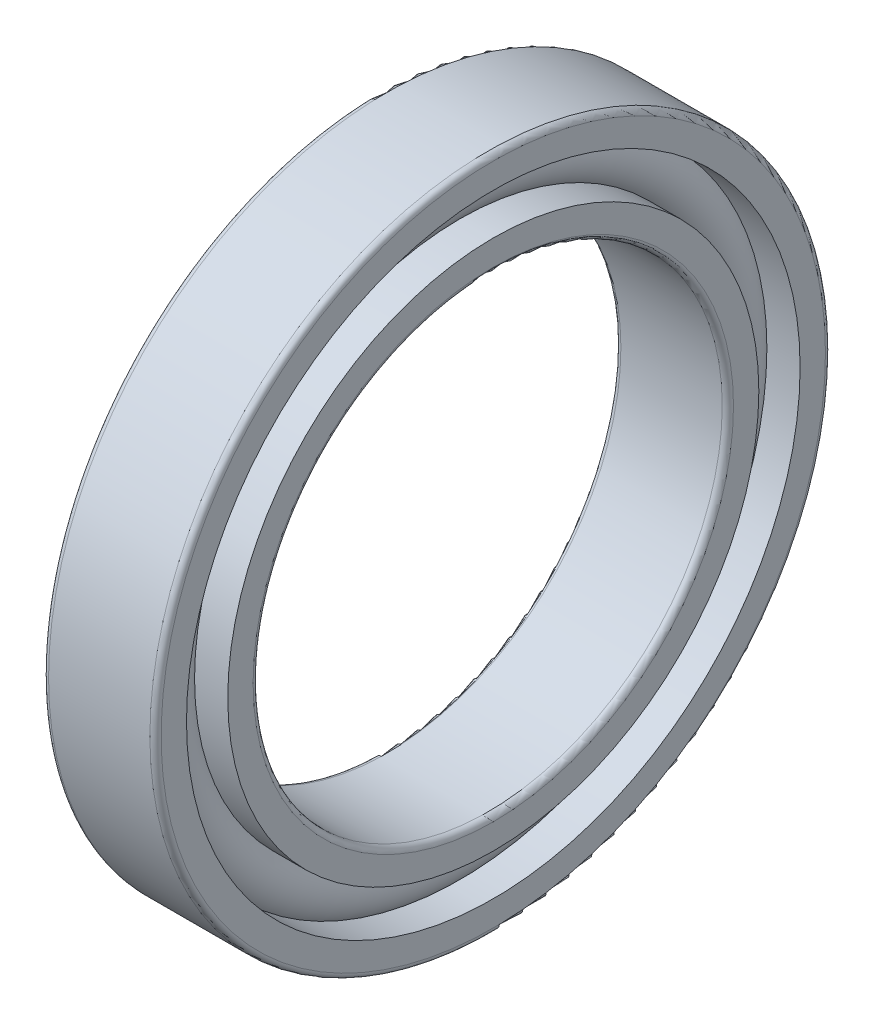
SolidWorks part; units mm, degrees
ref_plane "Plane1" through (0, 0, 0) normal (0, 0, 1) x (1, 0, 0)
ref_plane "Plane2" through (0, 0, 0) normal (0, 1, 0) x (1, 0, 0)
ref_plane "Plane3" through (0, 0, 0) normal (1, 0, 0) x (0, 0, -1)
sketch "Clipboard" plane through (0, 0, 0) normal (0, 0, 1) x (1, 0, 0)
  line L0 (-10, 0) -> (10, 0) construction
  line L1 (0, 0) -> (22.3471, -0.7804)
  line L2 (0, 0) -> (30.4814, 1.0644)
  line L3 (0, 0) -> (22.3471, -0.7804)
  line L4 (0, 0) -> (-22.3573, -0.3902)
  dimension "BallCLRad" = 30.5
sketch "CagSpiSke" plane through (0, 0, 0) normal (0, 0, 1) x (1, 0, 0)
  line L0 (0.33, 29.95) -> (0.33, 31.05)
  line L1 (0.33, 31.05) -> (-0.33, 31.05)
  line L2 (-0.33, 31.05) -> (-0.33, 29.95)
  line L3 (-0.33, 29.95) -> (0.33, 29.95)
  line L4 (-20.6375, 0) -> (20.6375, 0) construction
  line L5 (0, 0) -> (0, 23.7692) construction
  dimension "OD" = 62.1
  dimension "ID" = 59.9
revolve "CageSpine" add sketch "CagSpiSke" angle 0.001 about L4 reverse direction yes
ref_axis "Axis1" through (-50, 0, 0) along (1, 0, 0)
sketch "CagBalSke" plane through (0, 0, 0) normal (0, 0, 1) x (1, 0, 0)
  line L0 (-3.63, 30.5) -> (3.63, 30.5)
  line L1 (-1.905, 30.5) -> (1.905, 30.5) construction
  line L2 (-10, 0) -> (10, 0) construction
  line L3 (0, 0) -> (0, 24) construction
  arc A0 (3.63, 30.5) -> (-3.63, 30.5) centre (0, 30.5) cw
  dimension "BallCLRad" = 30.5
revolve "CageBall" [suppressed] add sketch "CagBalSke" angle 360 about L1 reverse direction yes
pattern_circular "CageBalls" [suppressed] count 2 every 180 about axis through (-50, 0, 0) along (1, 0, 0)
sketch "CagTrmODSke" plane through (0, 0, 0) normal (0, 0, 1) x (1, 0, 0)
  line L0 (3.631, 31.05) -> (3.631, 34.131)
  line L1 (3.631, 34.131) -> (-3.631, 34.131)
  line L2 (-3.631, 34.131) -> (-3.631, 31.05)
  line L3 (-3.631, 31.05) -> (3.631, 31.05)
  line L4 (-20.6375, 0) -> (20.6375, 0) construction
  line L5 (0, 0) -> (0, 25) construction
  dimension "Width" = 7.262
  dimension "ID" = 62.1
  dimension "OD" = 68.262
revolve "CageTrimOD" [suppressed] cut sketch "CagTrmODSke" angle 360 about L4 reverse direction yes
sketch "CagTrmIDSke" plane through (0, 0, 0) normal (0, 0, 1) x (1, 0, 0)
  line L0 (3.631, 26.871) -> (3.631, 29.95)
  line L1 (3.631, 29.95) -> (-3.631, 29.95)
  line L2 (-3.631, 29.95) -> (-3.631, 26.871)
  line L3 (-3.631, 26.871) -> (3.631, 26.871)
  line L4 (-20.6375, 0) -> (20.6375, 0) construction
  line L5 (0, 0) -> (0, 25) construction
  dimension "Width" = 7.262
  dimension "ID" = 53.742
  dimension "OD" = 59.9
revolve "CageTrimID" [suppressed] cut sketch "CagTrmIDSke" angle 360 about L4 reverse direction yes
sketch "BalSimSke" plane through (0, 0, 0) normal (0, 0, 1) x (1, 0, 0)
  line L0 (-10, 0) -> (10, 0) construction
  line L1 (-10, 30.5) -> (10, 30.5) construction
  line L2 (0, 0) -> (0, 23) construction
  circle A0 centre (0, 30.5) radius 3.3
  dimension "BallCLRad" = 30.5
  dimension "Ball_diameter" = 6.6
revolve "BallsSimplified" add sketch "BalSimSke" angle 360 about L0
sketch "BalDetSke" plane through (0, 0, 0) normal (0, 0, 1) x (1, 0, 0)
  line L0 (-3.3, 30.5) -> (3.3, 30.5)
  line L1 (-1.905, 30.5) -> (1.905, 30.5) construction
  line L2 (0, 0) -> (0, 25) construction
  arc A0 (3.3, 30.5) -> (-3.3, 30.5) centre (0, 30.5) cw
  dimension "BallCLRad" = 30.5
  dimension "Ball_diameter" = 6.6
revolve "BallDetailed" [suppressed] add sketch "BalDetSke" angle 360 about L1 reverse direction yes
sketch "InnRacSke" plane through (0, 0, 0) normal (0, 0, 1) x (1, 0, 0)
  line L0 (-2.426, 28.3) -> (-6, 28.3)
  line L1 (-6, 28.3) -> (-6, 25.6)
  line L2 (-5.4, 25) -> (5.4, 25)
  line L3 (6, 25.6) -> (6, 28.3)
  line L4 (6, 28.3) -> (2.426, 28.3)
  line L5 (-20.6375, 0) -> (20.6375, 0) construction
  line L6 (0, 0) -> (0, 30) construction
  arc A0 (-6, 25.6) -> (-5.4, 25) centre (-5.4, 25.6) ccw
  arc A1 (5.4, 25) -> (6, 25.6) centre (5.4, 25.6) ccw
  arc A2 (2.426, 28.3) -> (-2.426, 28.3) centre (0, 30.5) cw
  dimension "BallCLRad" = 30.5
  dimension "Fillet_radius" = 0.6
  dimension "Ball_diameter" = 6.55
  dimension "ID" = 50
  dimension "OD" = 56.6
  dimension "Width" = 12
revolve "InnerRace" add sketch "InnRacSke" angle 360 about L5 reverse direction yes
sketch "OutRacSke" plane through (0, 0, 0) normal (0, 0, 1) x (1, 0, 0)
  line L0 (-2.426, 32.7) -> (-6, 32.7)
  line L1 (-6, 32.7) -> (-6, 35.4)
  line L2 (-5.4, 36) -> (5.4, 36)
  line L3 (6, 35.4) -> (6, 32.7)
  line L4 (6, 32.7) -> (2.426, 32.7)
  line L5 (-20.6375, 0) -> (20.6375, 0) construction
  line L6 (0, 0) -> (0, 30) construction
  arc A0 (-6, 35.4) -> (-5.4, 36) centre (-5.4, 35.4) cw
  arc A1 (5.4, 36) -> (6, 35.4) centre (5.4, 35.4) cw
  arc A2 (2.426, 32.7) -> (-2.426, 32.7) centre (0, 30.5) ccw
  dimension "BallCLRad" = 30.5
  dimension "Fillet_radius" = 0.6
  dimension "Ball_diameter" = 6.55
  dimension "Width" = 12
revolve "OuterRace" add sketch "OutRacSke" angle 360 about L5 reverse direction yes
pattern_circular "BallsDetailed" [suppressed] count 2 every 180 about axis through (-50, 0, 0) along (1, 0, 0)
equation "\"BallCLRad@Clipboard\" = ( \"OD@OutRacSke\" + \"ID@InnRacSke\" ) / 4"
equation "\"BallCLRad@BalSimSke\" = \"BallCLRad@Clipboard\""
equation "\"BallCLRad@BalDetSke\" = \"BallCLRad@Clipboard\""
equation "\"BallCLRad@InnRacSke\" = \"BallCLRad@Clipboard\""
equation "\"BallCLRad@OutRacSke\" = \"BallCLRad@Clipboard\""
equation "\"Ball_diameter@InnRacSke\" = \"Ball_diameter@BalDetSke\" - 0.05"
equation "\"Ball_diameter@OutRacSke\" = \"Ball_diameter@BalDetSke\" - 0.05"
equation "\"Ball_diameter@BalSimSke\" = \"Ball_diameter@BalDetSke\""
equation "\"Width@OutRacSke\" = \"Width@InnRacSke\""
equation "\"Fillet_radius@OutRacSke\" = \"Fillet_radius@InnRacSke\""
equation "\"Max_count@Clipboard\" = int( 3.14159265 / atn(( \"Ball_diameter@BalDetSke\" / 2) / sqr( \"BallCLRad@Clipboard\"  *  \"BallCLRad@Clipboard\" - ( \"Ball_diameter@BalDetSke\" / 2) *  ( \"Ball_diameter@BalDetSke\" / 2))))"
equation "\"Max_count@Clipboard\" = ((sgn( \"Max_count@Clipboard\" - \"Count@Clipboard\" )-1)*( \"Max_count@Clipboard\" - \"Count@Clipboard\" ))/-2+ \"Count@Clipboard\""
equation "\"Count@BallsDetailed\" = int( \"Show_count@Clipboard\" ) "
equation "\"Count@BallsDetailed\" = ((sgn( \"Count@BallsDetailed\" - \"Max_count@Clipboard\" )-1)*( \"Count@BallsDetailed\" - \"Max_count@Clipboard\" ))/-2+ \"Max_count@Clipboard\""
equation "\"Count@BallsDetailed\" = ((sgn( \"Count@BallsDetailed\" - \"Min_count@Clipboard\" )+1)*( \"Count@BallsDetailed\" - \"Min_count@Clipboard\"))/2 +\"Min_count@Clipboard\""
equation "\"Angle@BallsDetailed\" = 360.0 / \"Max_count@Clipboard\""
equation "\"BallCLRad@CagBalSke\" = \"BallCLRad@Clipboard\""
equation "\"Count@CageBalls\" = \"Count@BallsDetailed\""
equation "\"Angle@CageBalls\" = \"Angle@BallsDetailed\""
equation "\"Angle@CageSpine\" =  \"Angle@CageBalls\" * ( \"Count@CageBalls\" -1 + int( \"Count@CageBalls\" / \"Max_count@Clipboard\" ) )  + 0.001 -  int( \"Count@CageBalls\" / \"Max_count@Clipboard\" ) * 0.001"
equation "\"Angle@CageSpine\" =  \"Angle@CageSpine\" * int( \"Min_count@Clipboard\" / 2) + int(1 / \"Min_count@Clipboard\")  * 0.001"
equation "\"CageWallOD@CagBalSke\" =  \"Ball_diameter@BalDetSke\" * 1.1"
equation "\"Thickness@CagSpiSke\" =  \"Ball_diameter@BalDetSke\" * 0.1"
equation "\"OD@CagTrmODSke\" = \"BallCLRad@Clipboard\" * 2 + \"CageWallOD@CagBalSke\" + 0.002"
equation "\"ID@CagTrmODSke\" = \"BallCLRad@Clipboard\" * 2 + \"Ball_diameter@BalDetSke\" / 6"
equation "\"OD@CagTrmIDSke\" = \"BallCLRad@Clipboard\" * 2 - \"Ball_diameter@BalDetSke\" / 6"
equation "\"ID@CagTrmIDSke\" = \"BallCLRad@Clipboard\" * 2 - \"CageWallOD@CagBalSke\" + 0.002"
equation "\"OD@CagSpiSke\" = \"ID@CagTrmODSke\""
equation "\"ID@CagSpiSke\" = \"OD@CagTrmIDSke\""
equation "\"Width@CagTrmODSke\" = \"CageWallOD@CagBalSke\" + 0.002"
equation "\"Width@CagTrmIDSke\" = \"CageWallOD@CagBalSke\" + 0.002"
